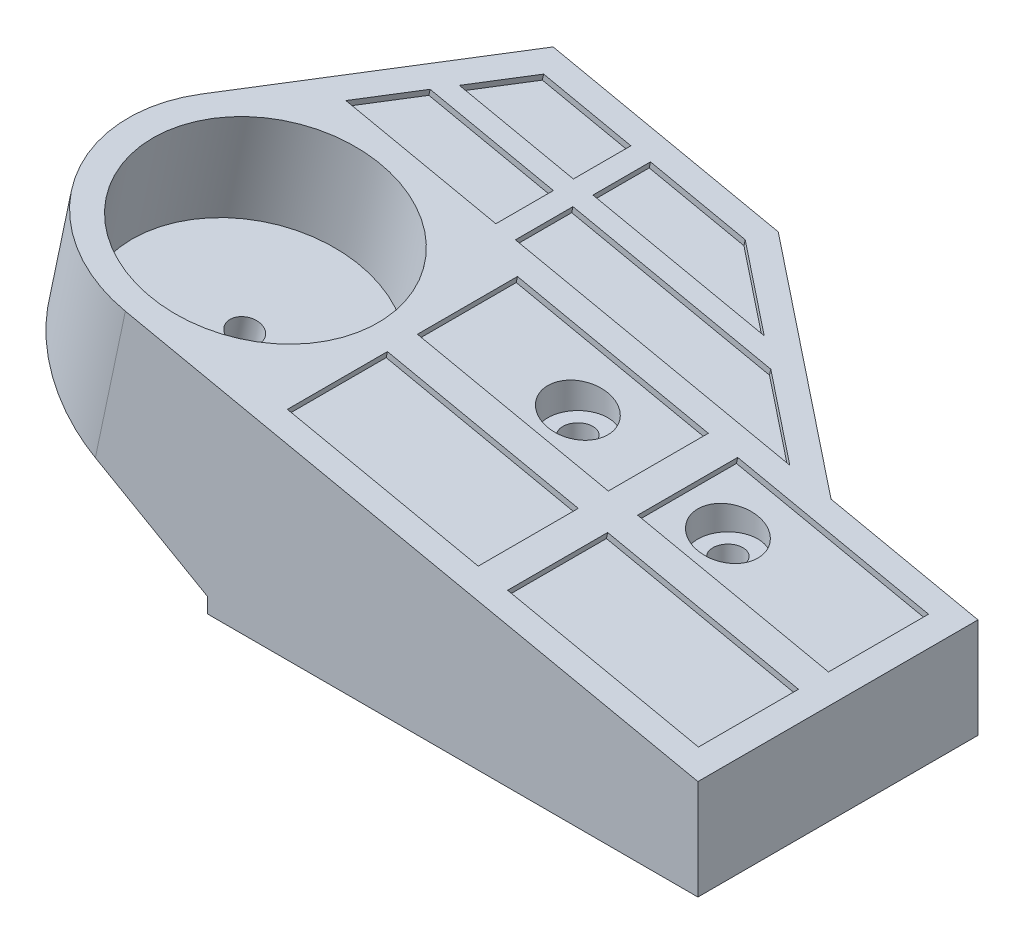
SolidWorks part; units mm, degrees
note: The reader was unsure of these and kept them because the rebuilt part matched: shared geometry of "Sketch2<3>".
ref_plane "Front" through (0, 0, 0) normal (0, 0, 1) x (1, 0, 0)
ref_plane "Top" through (0, 0, 0) normal (0, 1, 0) x (1, 0, 0)
ref_plane "Right" through (0, 0, 0) normal (1, 0, 0) x (0, 0, -1)
sketch "Sketch1" plane through (0, 0, 0) normal (0, 0, 1) x (1, 0, 0)
  line L0 (0, 0) -> (49, 0)
  line L1 (49, 0) -> (49, 10)
  line L2 (49, 10) -> (-21.931, 25)
  line L3 (-21.931, 25) -> (-24, 15.2164)
  line L4 (-24, 15.2164) -> (0, 1.5)
  line L5 (0, 1.5) -> (0, 0)
  dimension "D1" = 49
  dimension "D2" = 10
  dimension "D3" = 10
  dimension "D4" = 25
  dimension "D5" = 24
  dimension "D6" = 1.5
extrude "Boss-Extrude1" add sketch "Sketch1" along normal blind 28
sketch "Sketch2" plane through (4.1217, 19.4905, 0) normal (0.2069, 0.9784, 0) x (0.9784, -0.2069, 0)
  line L0 (45.8708, 0) -> (-26.6289, 0) construction
  line L1 (45.8708, -28) -> (-26.6289, -28) construction
  line L2 (-26.6289, -28) -> (-26.6289, 0) construction
  line L3 (-21.4833, 0) -> (-26.6289, 0)
  line L4 (-26.6289, 0) -> (-26.6289, -28)
  line L5 (-26.6289, -28) -> (-12.6289, -28)
  line L6 (-25.278, -8) -> (-13.8938, 16)
  line L7 (-13.8938, 16) -> (9.1062, 16)
  line L8 (9.1062, 16) -> (30.8547, 0)
  line L9 (45.8708, 0) -> (-26.6289, 0)
  arc A0 (-25.278, -8) -> (-12.6289, -28) centre (-12.6289, -14) ccw
  line M4 (45.8708, 0) -> (-26.6289, 0)
  line M5 (-26.6289, 0) -> (-26.6289, -28)
  line M6 (-26.6289, -28) -> (45.8708, -28)
  dimension "D1" = 16
  dimension "D2" = 23
  dimension "D3" = 27
  dimension "D4" = 6
extrude "Boss-Extrude2" add sketch "Sketch2" against normal blind 10 contours L8 L7 L6 M4
extrude "Cut-Extrude1" cut sketch "Sketch2<3>" against normal through all and the other way through all contours A0 L4 M6 | A0 L6 M4 M5
sketch "Sketch2<3>" plane through (4.1217, 19.4905, 0) normal (0.2069, 0.9784, 0) x (0.9784, -0.2069, 0) same geometry as "Sketch2"
sketch "Sketch3" plane through (4.1217, 19.4905, 0) normal (0.2069, 0.9784, 0) x (0.9784, -0.2069, 0)
  circle A0 centre (-12.6289, -14) radius 11.5
  dimension "D1" = 23
extrude "Cut-Extrude2" cut sketch "Sketch3" against normal blind 10
sketch "Sketch4" plane through (0, 0, 0) normal (0, -1, 0) x (1, 0, 0)
  line L0 (49, 28) -> (49, 0) construction
  line L1 (0, 28) -> (49, 28) construction
  circle A0 centre (17, 8) radius 1.5
  circle A1 centre (32, 8) radius 1.5
  dimension "D1" = 3
  dimension "D2" = 3
  dimension "D3" = 17
  dimension "D4" = 15
  dimension "D5" = 20
extrude "Cut-Extrude3" cut sketch "Sketch4" against normal through all
sketch "Sketch5" plane through (4.1217, 19.4905, 0) normal (0.2069, 0.9784, 0) x (0.9784, -0.2069, 0)
  line L0 (45.8708, -14) -> (-1.1289, -14) construction
  line L1 (45.8708, -28) -> (45.8708, 0) construction
  line L2 (22.3709, -28) -> (22.3709, 0) construction
  line L3 (45.8708, -28) -> (-12.6289, -28) construction
  line L4 (45.8708, -12.5) -> (-1.1289, -12.5)
  line L5 (45.8708, -15.5) -> (-1.1289, -15.5)
  line L6 (45.8708, -2.5) -> (-1.1289, -2.5)
  line L7 (45.8708, -25.5) -> (-1.1289, -25.5)
  line L8 (43.3709, -28) -> (43.3709, 0)
  line L9 (1.3709, -28) -> (1.3709, 0)
  line L10 (23.8709, -28) -> (23.8709, 0)
  line L11 (20.8709, -28) -> (20.8709, 0)
  line L12 (21.6795, 6.75) -> (-18.2815, 6.75) construction
  line L13 (9.1062, 16) -> (30.8547, 0) construction
  line L14 (-25.278, -8) -> (-13.8938, 16) construction
  line L15 (-2.3938, 16) -> (-2.3938, 0) construction
  line L16 (-13.8938, 16) -> (9.1062, 16) construction
  line L24 (30.8547, 0) -> (-18.7163, 0)
  line L25 (-3.3938, 16) -> (-3.3938, 0)
  line L26 (8.2856, 13.5) -> (29.3732, -2.0138)
  line L27 (-12.3127, 13.5) -> (8.2856, 13.5)
  line L28 (-23.0193, -9.0714) -> (-12.3127, 13.5)
  line L29 (8.2856, 13.5) -> (29.3732, -2.0138)
  line L30 (-12.3127, 13.5) -> (8.2856, 13.5)
  line L31 (-23.0193, -9.0714) -> (-12.3127, 13.5)
  line L32 (-1.3938, 16) -> (-1.3938, 0)
  line L33 (21.6795, 7.75) -> (-18.2815, 7.75)
  line L34 (21.6795, 5.75) -> (-18.2815, 5.75)
  circle A0 centre (-12.6289, -14) radius 11.5 construction
  point P9 (22.3709, -14)
  point P10 (22.3709, -14)
  ellipse M11 centre (13.1631, -8) end of major axis (14.6963, -8) minor radius 1.5
  ellipse M12 centre (28.4948, -8) end of major axis (30.028, -8) minor radius 1.5
  dimension "D1" = 1.5
  dimension "D9" = 2.5
  dimension "D10" = 6.75
  dimension "D2" = 1.5
  dimension "D3" = 10
  dimension "D4" = 10
  dimension "D5" = 21
  dimension "D6" = 21
  dimension "D7" = 1.5
  dimension "D8" = 1.5
  dimension "D11" = 1
  dimension "D12" = 1
  dimension "D13" = 1
  dimension "D14" = 1
extrude "Cut-Extrude4" cut sketch "Sketch5" against normal blind 0.6 contours L25 L34 L31 L24 | L33 L25 L30 L31 | L33 L29 L30 L32 | L29 L34 L32 L24 | L4 L11 L6 L9 M11 | L7 L11 L5 L9 | L10 L7 L8 L5 | L10 L4 L8 L6 M12 | M11 | M12
ref_plane "Plane1" through (0, 14, 0) normal (0, -1, 0) x (-1, 0, 0)
sketch "Sketch6" plane through (0, 14, 0) normal (0, -1, 0) x (-1, 0, 0)
  circle A0 centre (-17, -8) radius 3
  dimension "D1" = 6
extrude "Cut-Extrude5" cut sketch "Sketch6" against normal up to next
ref_plane "Plane2" through (0, 11, 0) normal (0, -1, 0) x (-1, 0, 0)
sketch "Sketch7" plane through (0, 11, 0) normal (0, -1, 0) x (-1, 0, 0)
  circle A0 centre (-32, -8) radius 3
  dimension "D1" = 6
extrude "Cut-Extrude6" cut sketch "Sketch7" against normal up to next
sketch "Sketch8" plane through (2.0528, 9.7069, 0) normal (0.2069, 0.9784, 0) x (0.9784, -0.2069, 0)
  circle A0 centre (-12.6289, -14) radius 1.5
  dimension "D1" = 3
extrude "Cut-Extrude7" cut sketch "Sketch8" against normal up to next
ref_plane "Plane3" through (1.3286, 6.2826, 0) normal (0.2069, 0.9784, 0) x (0.9784, -0.2069, 0)
sketch "Sketch9" plane through (1.3286, 6.2826, 0) normal (0.2069, 0.9784, 0) x (0.9784, -0.2069, 0)
  circle A0 centre (-12.6289, -14) radius 3
  dimension "D1" = 6
extrude "Cut-Extrude8" cut sketch "Sketch9" against normal up to next
